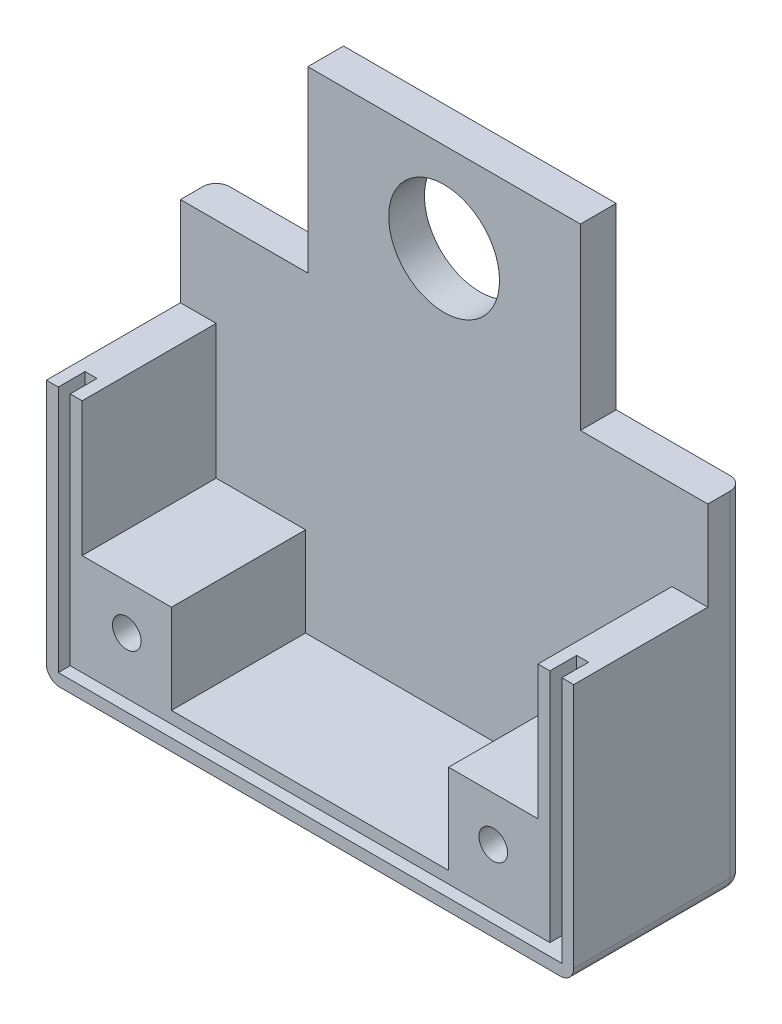
SolidWorks part; units mm, degrees
ref_plane "Płaszczyzna przednia" through (0, 0, 0) normal (0, 0, 1) x (1, 0, 0)
ref_plane "Płaszczyzna górna" through (0, 0, 0) normal (0, 1, 0) x (1, 0, 0)
ref_plane "Płaszczyzna prawa" through (0, 0, 0) normal (1, 0, 0) x (0, 0, -1)
sketch "Sketch1" plane through (0, 0, 0) normal (0, 0, 1) x (1, 0, 0)
  line L1 (-15.25, -10) -> (15.25, -10)
  line L2 (-15.25, -10) -> (-15.25, 10)
  line L3 (-15.25, 10) -> (15.25, 10)
  line L4 (15.25, -10) -> (15.25, 10)
  line L5 (-15.25, -10) -> (15.25, 10) construction
  line L6 (-15.25, 10) -> (15.25, -10) construction
  circle A0 centre (0, 0) radius 6.2
  point P0 (0, 0)
  dimension "D1" = 30.5
  dimension "D2" = 20
extrude "Boss-Extrude1" add sketch "Sketch1" along normal blind 4
sketch "Sketch2" plane through (0, -10, 0) normal (0, -1, 0) x (1, 0, 0)
  line L0 (-15.25, 4) -> (15.25, 0) construction
  line L1 (15.25, 0) -> (15.25, 4) construction
  line L2 (15.25, 4) -> (-15.25, 0) construction
  line L3 (-15.25, 0) -> (-15.25, 4) construction
  line L5 (-29.5, 0) -> (29.5, 0)
  line L6 (-29.5, 0) -> (-29.5, 4)
  line L7 (-29.5, 4) -> (29.5, 4)
  line L8 (29.5, 0) -> (29.5, 4)
  line L9 (-29.5, 0) -> (29.5, 4) construction
  line L10 (-29.5, 4) -> (29.5, 0) construction
  point P6 (0, 2)
  dimension "D1" = 59
extrude "Boss-Extrude2" add sketch "Sketch2" along normal blind 35
sketch "Sketch4" plane through (0, -45, 0) normal (0, -1, 0) x (1, 0, 0)
  line L1 (-29.5, 4) -> (29.5, 4)
  line L2 (-29.5, 4) -> (-29.5, 0)
  line L3 (-29.5, 0) -> (29.5, 0)
  line L4 (29.5, 4) -> (29.5, 0)
extrude "Boss-Extrude3" add sketch "Sketch4" along normal blind 4
sketch "Sketch5" plane through (0, 0, 4) normal (0, 0, 1) x (1, 0, 0)
  line L0 (29.5, -49) -> (29.5, -10) construction
  line L1 (-29.5, -49) -> (29.5, -49)
  line L2 (-29.5, -49) -> (-29.5, -45)
  line L3 (-29.5, -45) -> (29.5, -45)
  line L4 (29.5, -49) -> (29.5, -45)
  line L6 (-29.5, -45) -> (-25.5, -45)
  line L7 (-29.5, -45) -> (-29.5, -20)
  line L8 (-29.5, -20) -> (-25.5, -20)
  line L9 (-25.5, -45) -> (-25.5, -20)
  line L10 (29.5, -45) -> (25.5, -45)
  line L11 (29.5, -45) -> (29.5, -20)
  line L12 (29.5, -20) -> (25.5, -20)
  line L13 (25.5, -45) -> (25.5, -20)
  line M5 (-29.5, -10) -> (-29.5, -49)
  line M6 (-29.5, -49) -> (29.5, -49)
  line M7 (29.5, -49) -> (29.5, -10)
  dimension "D1" = 4
  dimension "D2" = 4
  dimension "D3" = 25
  dimension "D4" = 4
  dimension "D5" = 25
extrude "Boss-Extrude4" add sketch "Sketch5" along normal blind 15 contours L3 L9 L8 M5 | L3 M5 M6 M7 | L13 L3 L12 M7 region at (0, -47, 4) region at (-27.5, -32.5, 4) region at (27.5, -32.5, 4)
sketch "Sketch6" plane through (0, 0, 19) normal (0, 0, 1) x (1, 0, 0)
  line L0 (-29.5, -20) -> (-25.5, -20) construction
  line L1 (-28.1667, -20) -> (-26.8333, -20)
  line L2 (-28.1667, -20) -> (-28.1667, -47.6667)
  line L3 (-28.1667, -47.6667) -> (-26.8333, -47.6667)
  line L4 (-26.8333, -20) -> (-26.8333, -47.6667)
  line L5 (-29.5, -20) -> (-29.5, -49) construction
  line L6 (-29.5, -49) -> (29.5, -49) construction
  line L7 (29.5, -49) -> (29.5, -20) construction
  line L8 (-26.8333, -47.6667) -> (28.1667, -47.6667)
  line L9 (-26.8333, -47.6667) -> (-26.8333, -46.3333)
  line L10 (-26.8333, -46.3333) -> (28.1667, -46.3333)
  line L11 (28.1667, -47.6667) -> (28.1667, -46.3333)
  line L12 (29.5, -20) -> (25.5, -20) construction
  line L13 (28.1667, -46.3333) -> (26.8333, -46.3333)
  line L14 (28.1667, -46.3333) -> (28.1667, -20)
  line L15 (28.1667, -20) -> (26.8333, -20)
  line L16 (26.8333, -46.3333) -> (26.8333, -20)
  line M9 (29.5, -20) -> (25.5, -20)
  line M13 (-25.5, -20) -> (-29.5, -20)
  dimension "D1" = 1.3333
  dimension "D2" = 1.3333
  dimension "D3" = 1.3333
  dimension "D4" = 1.3333
  dimension "D5" = 1.3333
  dimension "D6" = 1.3333
extrude "Cut-Extrude1" cut sketch "Sketch6" against normal blind 3 contours L4 L2 L3 M13 | L8 L11 L10 L4 | L16 L10 L14 M9 region at (-27.5, -33.8333, 19) region at (0.6667, -47, 19) region at (27.5, -33.1667, 19)
sketch "Sketch8" plane through (0, 0, 4) normal (0, 0, 1) x (1, 0, 0)
  line L1 (-25.5, -45) -> (-15.5, -45)
  line L2 (-25.5, -45) -> (-25.5, -35)
  line L3 (-25.5, -35) -> (-15.5, -35)
  line L4 (-15.5, -45) -> (-15.5, -35)
  line L5 (25.5, -45) -> (15.5, -45)
  line L6 (25.5, -45) -> (25.5, -35)
  line L7 (25.5, -35) -> (15.5, -35)
  line L8 (15.5, -45) -> (15.5, -35)
  dimension "D1" = 10
  dimension "D2" = 10
  dimension "D3" = 10
  dimension "D4" = 10
extrude "Boss-Extrude5" add sketch "Sketch8" along normal blind 15
sketch "Sketch9" plane through (0, 0, 19) normal (0, 0, 1) x (1, 0, 0)
  line L0 (-25.5, -35) -> (-15.5, -45) construction
  line L1 (-15.5, -45) -> (-20.5, -40) construction
  line L2 (25.5, -35) -> (15.5, -45) construction
  line L3 (15.5, -45) -> (20.5, -40) construction
  circle A0 centre (-20.5, -40) radius 1.6
  circle A1 centre (20.5, -40) radius 1.6
extrude "Cut-Extrude2" cut sketch "Sketch9" against normal blind 20
sketch "Sketch15" plane through (0, 0, 0) normal (0, 0, -1) x (-1, 0, 0)
  circle A0 centre (-20.5, -40) radius 4
  circle A1 centre (20.5, -40) radius 4
extrude "Cut-Extrude3" cut sketch "Sketch15" against normal blind 14
sketch "Sketch18" plane through (0, 0, 14) normal (0, 0, -1) x (-1, 0, 0)
  point P0 (-20.5, -40)
  point P3 (20.5, -40)
hole_wizard "CSK for M3 Countersunk Flat Head Screw2" positions "Sketch18" profile "Sketch17" countersink size "M3" standard "ISO" end condition through all
sketch "Sketch17" plane through (20.5, -40, 14) normal (1, 0, 0) x (0, 1, 0)
  line L0 (0, 0) -> (0, 5)
  line L1 (0, 5) -> (1.6, 5)
  line L2 (1.6, 5) -> (1.6, 1.55)
  line L3 (1.6, 1.55) -> (3.15, 0)
  line L5 (3.15, 0) -> (0, 0)
  line L6 (-1.6, 1.55) -> (-3.15, 0) construction
  line L11 (0, -6.35) -> (0, 107.95) construction
  dimension "Thru Hole Dia." = 3.2
  dimension "Thru Hole Depth" = 5
  dimension "Near C'Sink Dia." = 6.3
  dimension "Near C'Sink Angle" = 90
fillet "Fillet1" radius 1.5 3 edges at (29.5, -29.5, 0) (0, -49, 0) (-29.5, -29.5, 0) type face fillet first side face at (16.5, -40, 0) second side face at (-29.5, -26.3333, 7.6667) second side face at (0, -49, 9.5) second side face at (29.5, -26.3333, 7.6667)
fillet "Fillet2" radius 1.5 1 edges at (29.5, -49, 10.25) type face fillet first side face at (29.5, -26.3333, 8.1667) second side face at (-29.5, -26.3333, 8.1667) second side face at (0, -49, 10.25)
fillet "Fillet3" radius 1.5 1 edges at (-29.5, -49, 10.25) type face fillet first side face at (-29.5, -26.3333, 8.1667) second side face at (-0.75, -49, 10.25)
